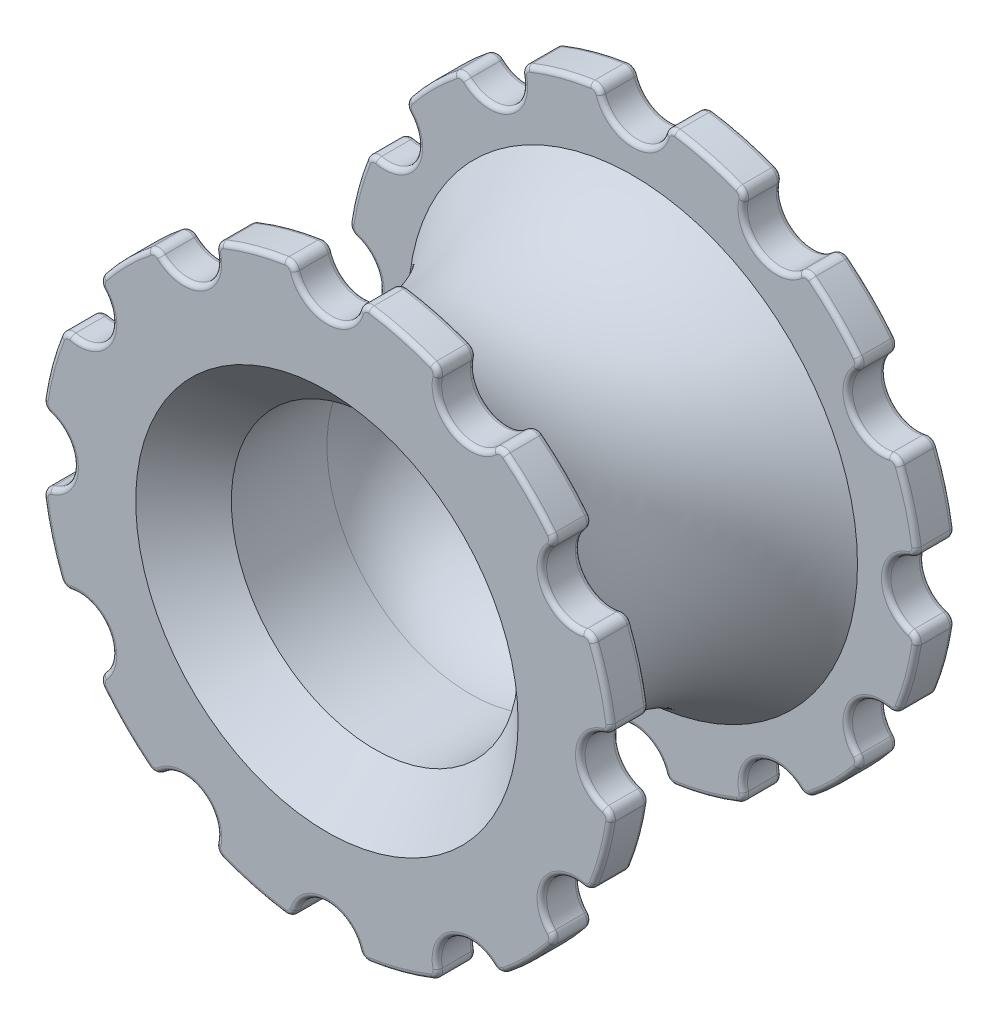
SolidWorks part; units mm, degrees
ref_plane "Спереди" through (0, 0, 0) normal (0, 0, 1) x (1, 0, 0)
ref_plane "Сверху" through (0, 0, 0) normal (0, 1, 0) x (1, 0, 0)
ref_plane "Справа" through (0, 0, 0) normal (1, 0, 0) x (0, 0, -1)
sketch "Эскиз1" plane through (0, 0, 0) normal (0, 0, 1) x (1, 0, 0)
  line L0 (0, -796.897) -> (0, 39047.9522) construction
  circle A0 centre (0, 0) radius 30 construction
  arc A1 (-3.494, 29.7958) -> (3.494, 29.7958) centre (0, 30) ccw
  arc A2 (3.494, 29.7958) -> (11.872, 27.551) centre (0, 0) cw
  arc A3 (11.872, 27.551) -> (17.9238, 24.0569) centre (15, 25.9808) ccw
  arc A4 (17.9238, 24.0569) -> (24.0569, 17.9238) centre (0, 0) cw
  arc A5 (24.0569, 17.9238) -> (27.551, 11.872) centre (25.9808, 15) ccw
  arc A6 (27.551, 11.872) -> (29.7958, 3.494) centre (0, 0) cw
  arc A7 (29.7958, 3.494) -> (29.7958, -3.494) centre (30, 0) ccw
  arc A8 (29.7958, -3.494) -> (27.551, -11.872) centre (0, 0) cw
  arc A9 (27.551, -11.872) -> (24.0569, -17.9238) centre (25.9808, -15) ccw
  arc A10 (24.0569, -17.9238) -> (17.9238, -24.0569) centre (0, 0) cw
  arc A11 (17.9238, -24.0569) -> (11.872, -27.551) centre (15, -25.9808) ccw
  arc A12 (11.872, -27.551) -> (3.494, -29.7958) centre (0, 0) cw
  arc A13 (3.494, -29.7958) -> (-3.494, -29.7958) centre (0, -30) ccw
  arc A14 (-3.494, -29.7958) -> (-11.872, -27.551) centre (0, 0) cw
  arc A15 (-11.872, -27.551) -> (-17.9238, -24.0569) centre (-15, -25.9808) ccw
  arc A16 (-17.9238, -24.0569) -> (-24.0569, -17.9238) centre (0, 0) cw
  arc A17 (-24.0569, -17.9238) -> (-27.551, -11.872) centre (-25.9808, -15) ccw
  arc A18 (-27.551, -11.872) -> (-29.7958, -3.494) centre (0, 0) cw
  arc A19 (-29.7958, -3.494) -> (-29.7958, 3.494) centre (-30, 0) ccw
  arc A20 (-29.7958, 3.494) -> (-27.551, 11.872) centre (0, 0) cw
  arc A21 (-27.551, 11.872) -> (-24.0569, 17.9238) centre (-25.9808, 15) ccw
  arc A22 (-24.0569, 17.9238) -> (-17.9238, 24.0569) centre (0, 0) cw
  arc A23 (-17.9238, 24.0569) -> (-11.872, 27.551) centre (-15, 25.9808) ccw
  arc A24 (-11.872, 27.551) -> (-3.494, 29.7958) centre (0, 0) cw
  point P55 (0, 0)
  dimension "D1" = 3.5
  dimension "D2" = 0
  dimension "D3" = 30
  dimension "D4" = 12
  dimension "D5" = 60
extrude "Бобышка-Вытянуть1" add sketch "Эскиз1" along normal blind 36
fillet "Скругление1" radius 1 24 edges at (3.494, 29.7958, 18) (11.872, 27.551, 18) (17.9238, 24.0569, 18) (29.7958, 3.494, 18) (27.551, 11.872, 18) (24.0569, 17.9238, 18) (29.7958, -3.494, 18) (27.551, -11.872, 18) (17.9238, -24.0569, 18) (24.0569, -17.9238, 18) (11.872, -27.551, 18) (-11.872, -27.551, 18) (3.494, -29.7958, 18) (-3.494, -29.7958, 18) (-17.9238, -24.0569, 18) (-24.0569, -17.9238, 18) (-27.551, -11.872, 18) (-29.7958, -3.494, 18) (-29.7958, 3.494, 18) (-27.551, 11.872, 18) (-24.0569, 17.9238, 18) (-17.9238, 24.0569, 18) (-11.872, 27.551, 18) (-3.494, 29.7958, 18)
sketch "Эскиз2" plane through (0, 0, 0) normal (0, 1, 0) x (1, 0, 0)
  line L0 (0, -1000) -> (0, 49000) construction
  line L2 (-30, -4) -> (-30, -32)
  line L5 (-30, -4) -> (-23.5, -4)
  line L6 (-30, -32) -> (-23.5, -32)
  arc A1 (-23.5, -4) -> (-23.5, -32) centre (-37.7829, -18) cw
  dimension "D3" = 6.5
  dimension "D5" = 20
  dimension "D1" = 4
  dimension "D2" = 28
  dimension "D4" = 30
revolve "Вырез-Повернуть1" cut sketch "Эскиз2" angle 360 about L0
sketch "Эскиз3" plane through (0, 0, 36) normal (0, 0, 1) x (1, 0, 0)
  circle A0 centre (0, 0) radius 15
  dimension "D1" = 30
extrude "Вырез-Вытянуть1" cut sketch "Эскиз3" against normal blind 25
fillet "Скругление2" radius 0.5 192 edges at (-29.5254, -3.7689, 4) (-26.5, 0, 4) (-29.5254, 3.7689, 4) (-28.9778, 7.7646, 4) (-27.4542, 11.4987, 4) (-22.9497, 13.25, 4) (-23.6853, 18.0266, 4) (-21.2132, 21.2132, 4) (-18.0266, 23.6853, 4) (-13.25, 22.9497, 4) (-11.4987, 27.4542, 4) (-7.7646, 28.9778, 4) (-3.7689, 29.5254, 4) (0, 26.5, 4) (3.7689, 29.5254, 4) (7.7646, 28.9778, 4) (11.4987, 27.4542, 4) (13.25, 22.9497, 4) (18.0266, 23.6853, 4) (21.2132, 21.2132, 4) (23.6853, 18.0266, 4) (22.9497, 13.25, 4) (27.4542, 11.4987, 4) (28.9778, 7.7646, 4) (29.5254, 3.7689, 4) (26.5, 0, 4) (29.5254, -3.7689, 4) (28.9778, -7.7646, 4) (27.4542, -11.4987, 4) (22.9497, -13.25, 4) (23.6853, -18.0266, 4) (21.2132, -21.2132, 4) (18.0266, -23.6853, 4) (13.25, -22.9497, 4) (11.4987, -27.4542, 4) (7.7646, -28.9778, 4) (3.7689, -29.5254, 4) (0, -26.5, 4) (-3.7689, -29.5254, 4) (-7.7646, -28.9778, 4) (-11.4987, -27.4542, 4) (-13.25, -22.9497, 4) (-18.0266, -23.6853, 4) (-21.2132, -21.2132, 4) (-23.6853, -18.0266, 4) (-22.9497, -13.25, 4) (-27.4542, -11.4987, 4) (-29.5254, -3.7689, 32) (-26.5, 0, 32) (-29.5254, 3.7689, 32) (-28.9778, 7.7646, 32) (-27.4542, 11.4987, 32) (-22.9497, 13.25, 32) (-23.6853, 18.0266, 32) (-21.2132, 21.2132, 32) (-18.0266, 23.6853, 32) (-13.25, 22.9497, 32) (-11.4987, 27.4542, 32) (-7.7646, 28.9778, 32) (-3.7689, 29.5254, 32) (0, 26.5, 32) (3.7689, 29.5254, 32) (7.7646, 28.9778, 32) (11.4987, 27.4542, 32) (13.25, 22.9497, 32) (18.0266, 23.6853, 32) (21.2132, 21.2132, 32) (23.6853, 18.0266, 32) (22.9497, 13.25, 32) (27.4542, 11.4987, 32) (28.9778, 7.7646, 32) (29.5254, 3.7689, 32) (26.5, 0, 32) (29.5254, -3.7689, 32) (28.9778, -7.7646, 32) (27.4542, -11.4987, 32) (22.9497, -13.25, 32) (23.6853, -18.0266, 32) (21.2132, -21.2132, 32) (18.0266, -23.6853, 32) (13.25, -22.9497, 32) (11.4987, -27.4542, 32) (7.7646, -28.9778, 32) (3.7689, -29.5254, 32) (0, -26.5, 32) (-3.7689, -29.5254, 32) (-7.7646, -28.9778, 32) (-11.4987, -27.4542, 32) (-13.25, -22.9497, 32) (-18.0266, -23.6853, 32) (-21.2132, -21.2132, 32) (-23.6853, -18.0266, 32) (-22.9497, -13.25, 32) (-27.4542, -11.4987, 32) (-29.5254, 3.7689, 36) (-28.9778, 7.7646, 36) (-27.4542, 11.4987, 36) (-22.9497, 13.25, 36) (-23.6853, 18.0266, 36) (-21.2132, 21.2132, 36) (-18.0266, 23.6853, 36) (-13.25, 22.9497, 36) (-11.4987, 27.4542, 36) (-7.7646, 28.9778, 36) (-3.7689, 29.5254, 36) (0, 26.5, 36) (3.7689, 29.5254, 36) (7.7646, 28.9778, 36) (11.4987, 27.4542, 36) (13.25, 22.9497, 36) (18.0266, 23.6853, 36) (21.2132, 21.2132, 36) (23.6853, 18.0266, 36) (22.9497, 13.25, 36) (27.4542, 11.4987, 36) (28.9778, 7.7646, 36) (29.5254, 3.7689, 36) (26.5, 0, 36) (29.5254, -3.7689, 36) (28.9778, -7.7646, 36) (27.4542, -11.4987, 36) (22.9497, -13.25, 36) (23.6853, -18.0266, 36) (21.2132, -21.2132, 36) (18.0266, -23.6853, 36) (13.25, -22.9497, 36) (11.4987, -27.4542, 36) (7.7646, -28.9778, 36) (3.7689, -29.5254, 36) (0, -26.5, 36) (-3.7689, -29.5254, 36) (-7.7646, -28.9778, 36) (-11.4987, -27.4542, 36) (-13.25, -22.9497, 36) (-18.0266, -23.6853, 36) (-21.2132, -21.2132, 36) (-23.6853, -18.0266, 36) (-22.9497, -13.25, 36) (-27.4542, -11.4987, 36) (-28.9778, -7.7646, 36) (-29.5254, -3.7689, 36) (3.7689, 29.5254, 0) (0, 26.5, 0) (-3.7689, 29.5254, 0) (-7.7646, 28.9778, 0) (-11.4987, 27.4542, 0) (-13.25, 22.9497, 0) (-18.0266, 23.6853, 0) (-21.2132, 21.2132, 0) (-23.6853, 18.0266, 0) (-22.9497, 13.25, 0) (-27.4542, 11.4987, 0) (-28.9778, 7.7646, 0) (-29.5254, 3.7689, 0) (-26.5, 0, 0) (-29.5254, -3.7689, 0) (-28.9778, -7.7646, 0) (-27.4542, -11.4987, 0) (-22.9497, -13.25, 0) (-23.6853, -18.0266, 0) (-21.2132, -21.2132, 0) (-18.0266, -23.6853, 0) (-13.25, -22.9497, 0) (-11.4987, -27.4542, 0) (-7.7646, -28.9778, 0) (-3.7689, -29.5254, 0) (0, -26.5, 0) (3.7689, -29.5254, 0) (7.7646, -28.9778, 0) (11.4987, -27.4542, 0) (13.25, -22.9497, 0) (18.0266, -23.6853, 0) (21.2132, -21.2132, 0) (23.6853, -18.0266, 0) (22.9497, -13.25, 0) (27.4542, -11.4987, 0) (28.9778, -7.7646, 0) (29.5254, -3.7689, 0) (26.5, 0, 0) (29.5254, 3.7689, 0) (28.9778, 7.7646, 0) (27.4542, 11.4987, 0) (22.9497, 13.25, 0) (23.6853, 18.0266, 0) (21.2132, 21.2132, 0) (18.0266, 23.6853, 0) (13.25, 22.9497, 0) (11.4987, 27.4542, 0) (7.7646, 28.9778, 0) (-28.9778, -7.7646, 4) (-28.9778, -7.7646, 32) (-26.5, 0, 36)
fillet "Скругление3" radius 10 1 edges at (15, 0, 11)
chamfer "Фаска1" distance 5 angle 45 1 edges at (15, 0, 36)
sketch "Эскиз4" plane through (0, 0, 0) normal (0, 0, -1) x (-1, 0, 0)
  circle A0 centre (0, 0) radius 6
  dimension "D1" = 12
extrude "Бобышка-Вытянуть2" add sketch "Эскиз4" along normal blind 1.5
sketch "Эскиз5" plane through (0, 0, -1.5) normal (0, 0, -1) x (-1, 0, 0)
  circle A0 centre (0, 0) radius 4.75
  dimension "D1" = 9.5
extrude "Бобышка-Вытянуть3" add sketch "Эскиз5" along normal blind 4.25
sketch "Эскиз6" plane through (0, 0, -5.75) normal (0, 0, -1) x (-1, 0, 0)
  circle A0 centre (0, 0) radius 1.5
  dimension "D1" = 3
extrude "Вырез-Вытянуть2" cut sketch "Эскиз6" against normal blind 38
